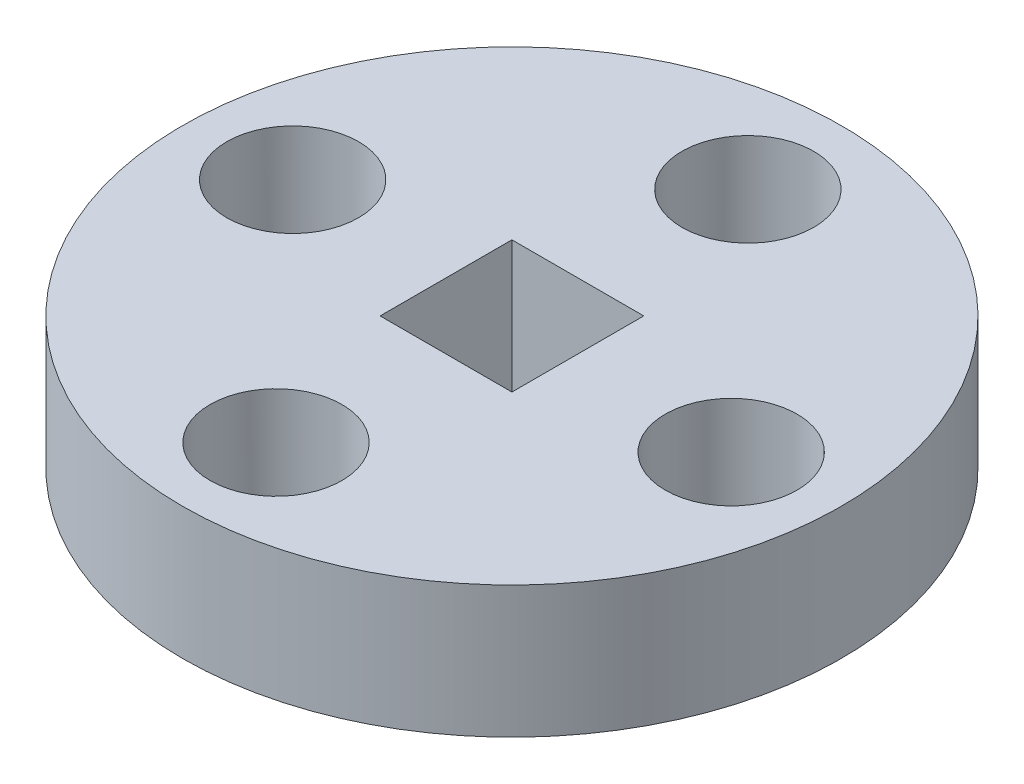
SolidWorks part; units mm, degrees
ref_plane "Ebene vorne" through (0, 0, 0) normal (0, 0, 1) x (1, 0, 0)
ref_plane "Ebene oben" through (0, 0, 0) normal (0, 1, 0) x (1, 0, 0)
ref_plane "Ebene rechts" through (0, 0, 0) normal (1, 0, 0) x (0, 0, -1)
sketch "Skizze1" plane through (0, 0, 0) normal (0, 1, 0) x (1, 0, 0)
  circle A0 centre (0, 0) radius 5
extrude "Aufsatz-Linear austragen1" add sketch "Skizze1" along normal blind 2
sketch "Skizze3" plane through (0, 2, 0) normal (0, 1, 0) x (1, 0, 0)
  line L0 (1, 1) -> (-1, 1)
  line L1 (1, 1) -> (1, -1)
  line L2 (1, -1) -> (-1, -1)
  line L3 (-1, 1) -> (-1, -1)
  line L4 (0, 0) -> (0, -2) construction
  line L5 (0, 0) -> (-10.1495, 0) construction
  point P8 (-1, 0)
  point P9 (0, -1)
extrude "Schnitt-Linear austragen1" cut sketch "Skizze3" against normal blind 3
sketch "Skizze4" plane through (0, 2, 0) normal (0, 1, 0) x (1, 0, 0)
  circle A0 centre (3.4528, -0.1264) radius 1
extrude "Schnitt-Linear austragen2" cut sketch "Skizze4" against normal blind 3
pattern_circular "Kreismuster1" count 4 over 360 about axis through (0, 2, 0) along (0, -1, 0) of "Schnitt-Linear austragen2"
